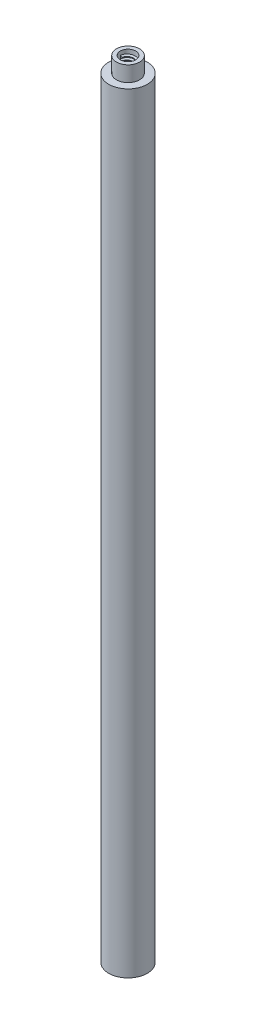
SolidWorks part; units mm, degrees
ref_plane "Ön Düzlem" through (0, 0, 0) normal (0, 0, 1) x (1, 0, 0)
ref_plane "Üst Düzlem" through (0, 0, 0) normal (0, 1, 0) x (1, 0, 0)
ref_plane "Sağ Düzlem" through (0, 0, 0) normal (1, 0, 0) x (0, 0, -1)
sketch "Çizim2" plane through (0, 0, 0) normal (0, 0, 1) x (1, 0, 0)
  line L0 (1, 100) -> (1, 102)
  line L1 (0, 0) -> (2.5, 0)
  line L2 (0, 0) -> (0, 100)
  line L3 (0, 100) -> (1, 100)
  line L5 (1, 102) -> (2.5, 102)
  line L6 (2.5, 0) -> (2.5, 102)
  line L7 (2.5, -8.5296) -> (2.5, 112.6434) construction
  dimension "D1" = 100
  dimension "D2" = 1.5
  dimension "D3" = 2.5
  dimension "D4" = 2
revolve "Döndür2" add sketch "Çizim2" angle 360 about L7
sketch "Çizim3" plane through (0, 102, 0) normal (0, 1, 0) x (1, 0, 0)
  circle A0 centre (2.5, 0) radius 1
extrude "Kes-Ekstrüzyon1" cut sketch "Çizim3" against normal blind 5
thread "Diş1" pitch 0.4 method extrude profile "Diş Profili1" start angle 0, offset 0.5, length 5, pitch 0.4, diameter 2
ref_plane "Düzlem1" through (1.5, 101.5, 0) normal (0, 0, 1) x (-1, 0, 0)
sketch "Diş Profili1" plane through (1.5, 101.5, 0) normal (0, 0, 1) x (-1, 0, 0)
  line L0 (0, 0) -> (0, 0.4) construction
  line L11 (0, 0) -> (0, 0.35)
  line L12 (0, 0.35) -> (-0.2165, 0.225)
  line L13 (-0.2165, 0.225) -> (-0.2165, 0.125)
  line L15 (-0.2165, 0.125) -> (0, 0)
  line L17 (-0.2165, 0.175) -> (0, 0.175) construction
  point P2 (0, 0)
  dimension "Pitch" = 0.4
  dimension "Profile_Angle" = 60
  dimension "Profile_Land" = 0.1
  dimension "Profile_Height" = 0.2165
